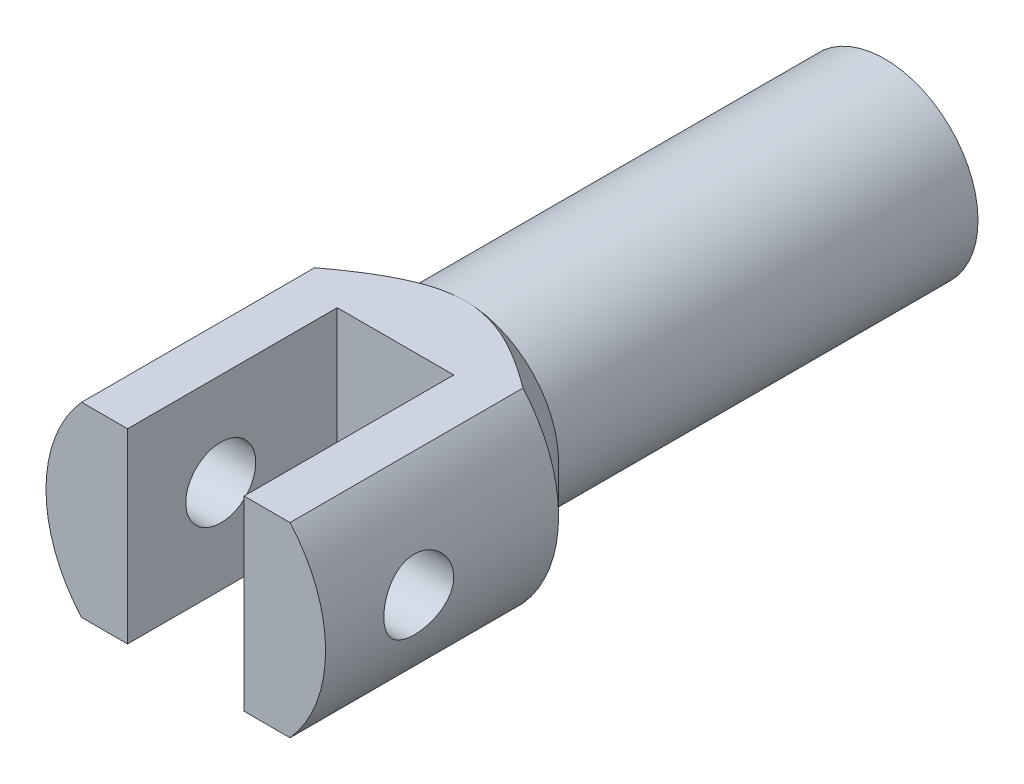
SolidWorks part; units mm, degrees
material "1060 合金"
ref_plane "前视基准面" through (0, 0, 0) normal (0, 0, 1) x (1, 0, 0)
ref_plane "上视基准面" through (0, 0, 0) normal (0, 1, 0) x (1, 0, 0)
ref_plane "右视基准面" through (0, 0, 0) normal (1, 0, 0) x (0, 0, -1)
sketch "草图1" plane through (0, 0, 0) normal (0, 0, 1) x (1, 0, 0)
  circle A0 centre (0, 0) radius 4
  dimension "D1" = 8
extrude "凸台-拉伸1" add sketch "草图1" along normal blind 20
sketch "草图9" plane through (0, 0, 20) normal (0, 0, 1) x (1, 0, 0)
  line L1 (-4.4721, -4) -> (4.4721, -4)
  line L2 (-4.4721, -4) -> (-4.4721, 4) construction
  line L3 (-4.4721, 4) -> (4.4721, 4)
  line L4 (4.4721, -4) -> (4.4721, 4) construction
  line L5 (-4.4721, -4) -> (4.4721, 4) construction
  line L6 (-4.4721, 4) -> (4.4721, -4) construction
  circle A0 centre (0, 0) radius 4 construction
  arc A1 (-4.4721, 4) -> (-4.4721, -4) centre (0, 0) ccw
  arc A2 (4.4721, -4) -> (4.4721, 4) centre (0, 0) ccw
  point P0 (0, 0)
  dimension "D1" = 6
extrude "凸台-拉伸3" add sketch "草图9" along normal blind 10
chamfer "倒角1" distance 2 angle 45 2 edges at (-4, 0, 20) (4, 0, 20)
sketch "草图10" plane through (0, 0, 30) normal (0, 0, 1) x (1, 0, 0)
  line L0 (0, 6.6752) -> (0, -6.9763)
extrude "切除-拉伸-薄壁1" cut sketch "草图10" against normal blind 9 thin thin type mid plane wall 5
hole_wizard "M4 螺纹孔1" positions "草图6" profile "草图7" tap size "M4" standard "GB"
sketch "草图6" plane through (0, 0, 0) normal (0, 0, -1) x (-1, 0, 0)
  point P0 (0, 0)
sketch "草图7" plane through (0, 0, 0) normal (1, 0, 0) x (0, 1, 0)
  line L0 (0, 0) -> (0, 20.9914)
  line L1 (0, 20.9914) -> (1.65, 20)
  line L2 (1.65, 20) -> (1.65, 18)
  line L3 (1.65, 18) -> (2, 18)
  line L4 (2, 18) -> (2, 0)
  line L5 (2, 0) -> (0, 0)
  line L10 (0, 20.9914) -> (-1.65, 20) construction
  line L11 (0, -6.35) -> (0, 107.95) construction
  dimension "螺纹孔钻头直径" = 3.3
  dimension "螺纹孔钻头深度" = 20
  dimension "螺纹主直径" = 4
  dimension "螺纹深度" = 18
  dimension "导头角度" = 118
hole_wizard "M3 螺纹孔1" positions "草图12" profile "草图11" tap size "M3" standard "GB" end condition up to next
sketch "草图12" plane through (-2.5, 0, 0) normal (1, 0, 0) x (0, 0, -1)
  line L1 (-30, 4) -> (-30, -4) construction
  point P0 (-26, 0)
  point P8 (-30, 0)
  dimension "D1" = 4
sketch "草图11" plane through (-2.5, 0, 26) normal (0, 1, 0) x (0, 0, -1)
  line L0 (0, 0) -> (0, 3.5)
  line L1 (0, 3.5) -> (1.5, 3.5)
  line L2 (1.5, 3.5) -> (1.5, 0)
  line L5 (1.5, 0) -> (0, 0)
  line L11 (0, -6.35) -> (0, 107.95) construction
  dimension "螺纹线主直径" = 3
  dimension "通孔螺纹孔钻头深度" = 3.5
hole_wizard "M3 间隙孔1" positions "草图14" profile "草图13" hole size "M3" standard "GB" end condition up to next
sketch "草图14" plane through (2.5, 0, 0) normal (-1, 0, 0) x (0, 0, 1)
  point P0 (26, 0)
sketch "草图13" plane through (2.5, 0, 26) normal (0, 1, 0) x (0, 0, 1)
  line L0 (0, 0) -> (0, 3.5)
  line L1 (0, 3.5) -> (1.5, 3.5)
  line L2 (1.5, 3.5) -> (1.5, 0)
  line L5 (1.5, 0) -> (0, 0)
  line L11 (0, -6.35) -> (0, 107.95) construction
  dimension "通孔孔直径" = 3
  dimension "通孔孔深度" = 3.5
